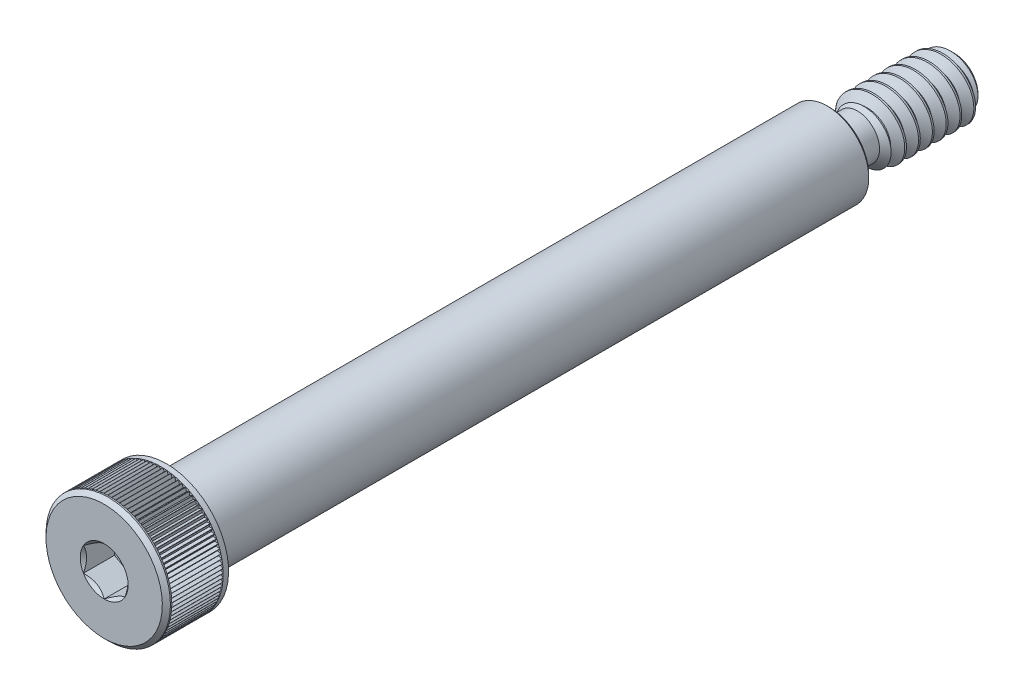
SolidWorks part; units mm, degrees
ref_plane "Front" through (0, 0, 0) normal (0, 0, 1) x (1, 0, 0)
ref_plane "Top" through (0, 0, 0) normal (0, 1, 0) x (1, 0, 0)
ref_plane "Right" through (0, 0, 0) normal (1, 0, 0) x (0, 0, -1)
sketch "Sketch1" plane through (0, 0, 0) normal (1, 0, 0) x (0, 0, -1)
  line L0 (0, 4.7625) -> (4.7625, 4.7625)
  line L1 (4.7625, 4.7625) -> (4.7625, 3.175)
  line L2 (4.7625, 3.175) -> (55.5625, 3.175)
  line L3 (55.5625, 3.175) -> (55.5625, 2.413)
  line L4 (55.5625, 2.413) -> (65.0875, 2.413)
  line L5 (65.0875, 2.413) -> (65.0875, 0)
  line L6 (65.0875, 0) -> (0, 0)
  line L7 (0, 0) -> (0, 4.7625)
  line L8 (0, 4.7625) -> (0, -4.7625) construction
  line L9 (65.0875, 2.413) -> (65.0875, -2.413) construction
  line L10 (55.5625, 3.175) -> (55.5625, -3.175) construction
  line L11 (65.0875, -2.413) -> (63.4097, -2.413) construction
  line L12 (30.1625, 0) -> (30.1625, 3.175) construction
  point P8 (63.5, -2.413)
  point P12 (55.5625, 0)
  point P17 (9.8425, 3.175)
  point P18 (30.1625, 0)
  point P19 (30.1625, 3.175)
  point P20 (50.4825, 3.175)
  point P21 (50.4825, -3.175)
  point P22 (9.8425, -3.175)
  dimension "Head Dia" = 9.525
  dimension "Head Ht" = 4.7625
  dimension "Thread Lg" = 9.525
  dimension "Thread Dia" = 4.826
  dimension "Shoulder Dia" = 6.35
  dimension "Shoulder Lg" = 50.8
  dimension "D1" = 1.5875
  dimension "D2" = 1.6778
  dimension "D3" = 25.4
  dimension "D4" = 5.08
revolve "Revolve1" add sketch "Sketch1" angle 360 mid plane about L6
ref_plane "Plane1" through (0, 0, -65.0875) normal (0, 0, 1) x (1, 0, 0)
sketch "Sketch3" plane through (0, 0, -65.0875) normal (0, 0, 1) x (1, 0, 0)
  circle A0 centre (0, 0) radius 2.413
sketch "Sketch5" plane through (0, 0, 0) normal (1, 0, 0) x (0, 0, -1)
  line L0 (55.5625, 3.175) -> (59.1566, 3.175)
  line L1 (59.1566, 3.175) -> (57.6707, 1.6891)
  line L2 (57.6707, 1.6891) -> (56.2864, 1.6891)
  line L3 (55.5625, 3.175) -> (55.5625, 2.413)
  line L5 (55.5625, 2.413) -> (65.0875, 2.413) construction
  line L6 (65.0875, 0) -> (57.6707, 0) construction
  line L7 (61.3791, 0) -> (61.3791, -2.413) construction
  arc A0 (55.5625, 2.413) -> (56.2864, 1.6891) centre (56.2864, 2.413) ccw
  dimension "D1" = 45
  dimension "CADB" = 2.1082
  dimension "CADA" = 3.3782
revolve "Cut-Revolve1" cut sketch "Sketch5" angle 360 mid plane about L6
chamfer "Chamfer1" distance 0.6032 angle 45 1 edges at (0, 2.413, -65.0875)
chamfer "Chamfer2" distance 0.3096 angle 45 1 edges at (0, 4.7625, 0)
chamfer "Chamfer3" distance 0.2032 angle 45 1 edges at (0, 3.175, -55.5625)
sketch "Sketch10" plane through (0, 0, 0) normal (1, 0, 0) x (0, 0, -1)
  line L0 (0.3096, 0) -> (4.4529, 0) construction
  line L1 (0.3096, -4.7625) -> (0.3096, 4.7625) construction
  line L3 (0.3096, 0) -> (0, 0) construction
  line L4 (4.4529, 0) -> (4.7625, 0) construction
  line L5 (4.7625, -4.7625) -> (4.7625, 4.7625) construction
  point P6 (2.3812, 0)
  dimension "D1" = 4.1434
ref_plane "Plane2" through (0, 0, -2.3812) normal (0, 0, 1) x (1, 0, 0)
sketch "Sketch11" plane through (0, 0, -2.3812) normal (0, 0, 1) x (1, 0, 0)
  line L0 (0, 4.5148) -> (0, 4.7625) construction
  line L1 (0, 4.5148) -> (0.143, 4.7625)
  line L2 (0, 4.5148) -> (-0.143, 4.7625)
  line L3 (-0.143, 4.7625) -> (0.143, 4.7625)
  line L4 (0, 0) -> (-0.143, 4.7625) construction
  line L5 (0.143, 4.7625) -> (0, 0) construction
  circle A1 centre (0, 0) radius 4.7625 construction
  circle A2 centre (0, 0) radius 4.5148 construction
  circle A3 centre (0, 0) radius 4.4529 construction
  point P3 (0, 0.0018)
  point P8 (2.3908, 0.7309)
  dimension "D1" = 0.2476
  dimension "D2" = 3.439
extrude "Cut-Extrude5" cut sketch "Sketch11" against normal mid plane 3.9362
pattern_circular "CirPattern1" count 99 over 360 about axis through (0, 0, -65.0875) along (0, 0, -1) of "Cut-Extrude5"
sketch "Sketch8" plane through (0, 0, 0) normal (0, 0, 1) x (1, 0, 0)
  line L1 (1.5875, 0.9165) -> (0, 1.8331)
  line L2 (0, 1.8331) -> (-1.5875, 0.9165)
  line L3 (-1.5875, 0.9165) -> (-1.5875, -0.9165)
  line L4 (-1.5875, -0.9165) -> (0, -1.8331)
  line L5 (0, -1.8331) -> (1.5875, -0.9165)
  line L6 (1.5875, -0.9165) -> (1.5875, 0.9165)
  circle A0 centre (0, 0) radius 1.5875 construction
  dimension "Hex" = 3.175
extrude "Cut-Extrude2" cut sketch "Sketch8" against normal blind 2.3813
sketch "Sketch9" plane through (0, 0, 0) normal (0, 0, 1) x (1, 0, 0)
  circle A0 centre (0, 0) radius 1.8331
extrude "Cut-Extrude4" cut sketch "Sketch9" against normal blind 2.3813 draft 45
sketch "Front Sketch" plane through (0, 0, 0) normal (0, 0, 1) x (1, 0, 0)
  line L0 (1.5875, -0.9165) -> (1.5875, 0.9165) construction
  line L1 (-1.5875, 0.9165) -> (-1.5875, -0.9165) construction
  circle A0 centre (0, 0) radius 4.7625 construction
  point P4 (-1.5875, 0)
  point P5 (1.5875, 0)
  point P6 (4.7625, 0)
  point P9 (-4.7625, 0)
ref_plane "Contact Plane 1" through (0, 0, -4.7625) normal (0, 0, -1) x (-1, 0, 0)
ref_axis "Center Axis 1" through (0, 0, -65.0875) along (0, 0, 1)
curve "Helix/Spiral1" pitch 1.0583 height 10.5833 radius 2.413 centre (0, 0, -65.0875) axis (0, 0, 1) start towards (0, 1, 0)
sketch "Sketch4" plane through (0, 0, 0) normal (1, 0, 0) x (0, 0, -1)
  line L0 (65.0214, 2.5276) -> (66.0797, 2.5276) construction
  line L1 (66.0797, 2.5276) -> (65.5505, 1.611) construction
  line L3 (65.5505, 1.611) -> (65.0214, 2.5276) construction
  line L4 (65.0544, 2.4703) -> (66.0466, 2.4703) construction
  line L5 (65.0875, 2.413) -> (66.0135, 2.413) construction
  line L6 (65.4844, 1.7256) -> (65.6167, 1.7256) construction
  line L7 (65.5505, 1.7256) -> (65.5505, 1.611) construction
  line L8 (65.5505, 2.5276) -> (65.5505, 2.413) construction
  line L9 (65.0544, 2.4703) -> (66.0466, 2.4703)
  line L10 (66.0466, 2.4703) -> (65.6167, 1.7256)
  line L11 (65.6167, 1.7256) -> (65.4844, 1.7256)
  line L12 (65.4844, 1.7256) -> (65.0544, 2.4703)
  point P14 (65.5505, 2.4703)
  point P15 (65.5505, 2.5276)
  dimension "D1" = 1.0583
  dimension "D2" = 0.1323
sweep "Cut-Sweep1" cut profiles "Sketch4" path "Helix/Spiral1" align with end faces yes
sketch "Sketch12" plane through (0, 0, 0) normal (1, 0, 0) x (0, 0, -1)
  line L1 (55.5625, 2.9718) -> (55.3593, 3.175)
  line L2 (55.3593, 3.175) -> (4.7625, 3.175)
  line L3 (4.7625, 3.175) -> (4.7625, 0)
  line L4 (4.7625, -4.7625) -> (4.7625, 4.7625) construction
  line L5 (4.7625, 0) -> (55.5625, 0)
  line L6 (55.5625, 2.9718) -> (55.5625, 2.413)
  line L7 (57.6707, 1.6891) -> (56.2864, 1.6891) construction
  line L8 (57.6707, 1.6891) -> (56.2864, 1.6891)
  line L9 (57.6707, 1.6891) -> (57.6707, 0)
  line L10 (57.6707, 0) -> (55.5625, 0)
  arc A0 (55.5625, 2.413) -> (56.2864, 1.6891) centre (56.2864, 2.413) ccw construction
  arc A1 (55.5625, 2.413) -> (56.2864, 1.6891) centre (56.2864, 2.413) ccw
revolve "Revolve2" add sketch "Sketch12" angle 360 about L5
equation "\"D3@Helix/Spiral1\" = \"Thread Lg@Sketch1\" + \"D4@Helix/Spiral1\""
equation "\"D1@Chamfer1\" = \"Thread Dia@Sketch1\" * .125"
equation "\"D1@Cut-Extrude2\"= \"Head Ht@Sketch1\" * .5"
equation "\"D1@Cut-Extrude4\" = \"D1@Cut-Extrude2\""
equation "\"D1@Chamfer2\" = \"Head Dia@Sketch1\" * .0325"
equation "\"D1@Sketch1\"=\"D4@Helix/Spiral1\"*1.5"
equation "\"D1@Sketch11\"=\"D1@Chamfer2\"*.8"
equation "\"D1@Cut-Extrude5\"=\"D1@Sketch10\"*.95"
equation "\"D1@CirPattern1\"=(360/\"D2@Sketch11\")-6"
equation "\"D3@Sketch1\"=\"Shoulder Lg@Sketch1\"/2"
equation "\"D4@Sketch1\"=\"D3@Sketch1\"*.2"
equation "\"D1@Sketch4\"=\"D4@Helix/Spiral1\""
equation "\"D2@Sketch4\"=\"D1@Sketch4\"/8"
